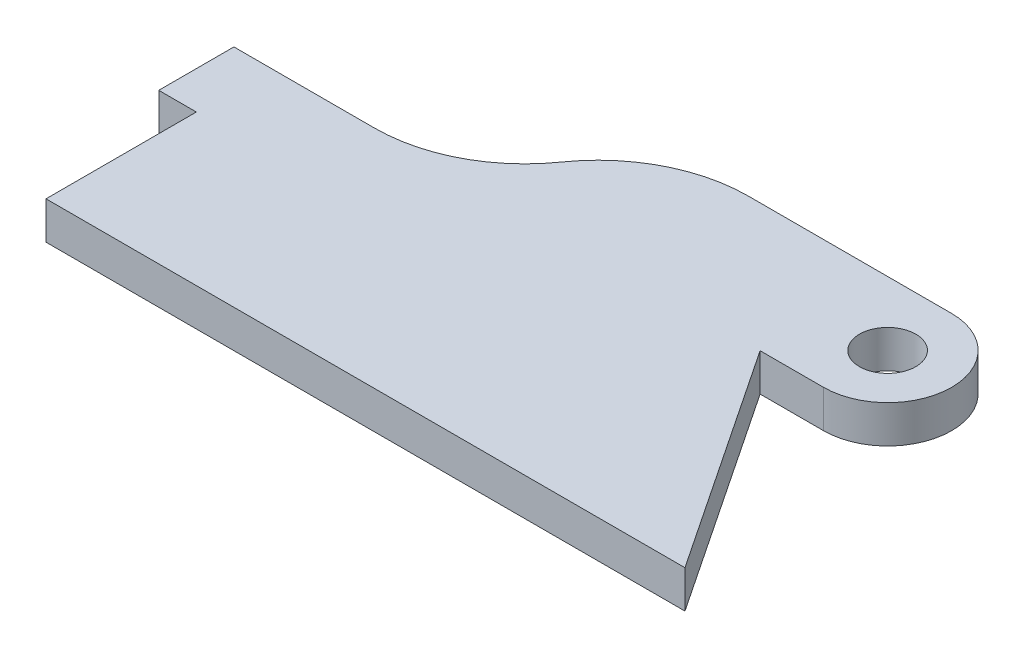
SolidWorks part; units mm, degrees
material "UHMW"
ref_plane "Front Plane" through (0, 0, 0) normal (0, 0, 1) x (1, 0, 0)
ref_plane "Top Plane" through (0, 0, 0) normal (0, 1, 0) x (1, 0, 0)
ref_plane "Right Plane" through (0, 0, 0) normal (1, 0, 0) x (0, 0, -1)
other "Bounding Box"
ref_plane "Default Plane" through (-8.9266, -12.7485, 0) normal (-0.1736, 0.9848, 0) x (0.9848, 0.1736, 0)
sketch "Sketch1" plane through (0, 0, 0) normal (0, 1, 0) x (1, 0, 0)
  line L0 (0, 0) -> (48.8289, 0)
  line L1 (88.9, 0) -> (114.3, -38.1)
  line L2 (114.3, -38.1) -> (6.35, -38.1)
  line L3 (6.35, -38.1) -> (6.35, -12.7)
  line L4 (6.35, -12.7) -> (0, -12.7)
  line L5 (0, -12.7) -> (0, 0)
  line L6 (99.6289, 0) -> (88.9, 0)
  line L7 (48.8289, 21.632) -> (48.8289, 0)
  line L9 (99.6289, 21.632) -> (48.8289, 21.632)
  circle A0 centre (99.6289, 10.816) radius 4.7625
  arc A1 (99.6289, 21.632) -> (99.6289, 0) centre (99.6289, 10.816) cw
  dimension "D7" = 50.8
  dimension "D8" = 9.525
  dimension "D9" = 10.7289
  dimension "D6" = 10.816
  dimension "D1" = 6.35
  dimension "D2" = 38.1
  dimension "D3" = 107.95
  dimension "D4" = 88.9
  dimension "D5" = 12.7
extrude "Boss-Extrude1" add sketch "Sketch1" along normal blind 6.35
fillet "Fillet1" radius 25.4 1 edges at (48.8289, 3.175, 0)
fillet "Fillet2" radius 25.4 1 edges at (48.8289, 3.175, -21.632)
